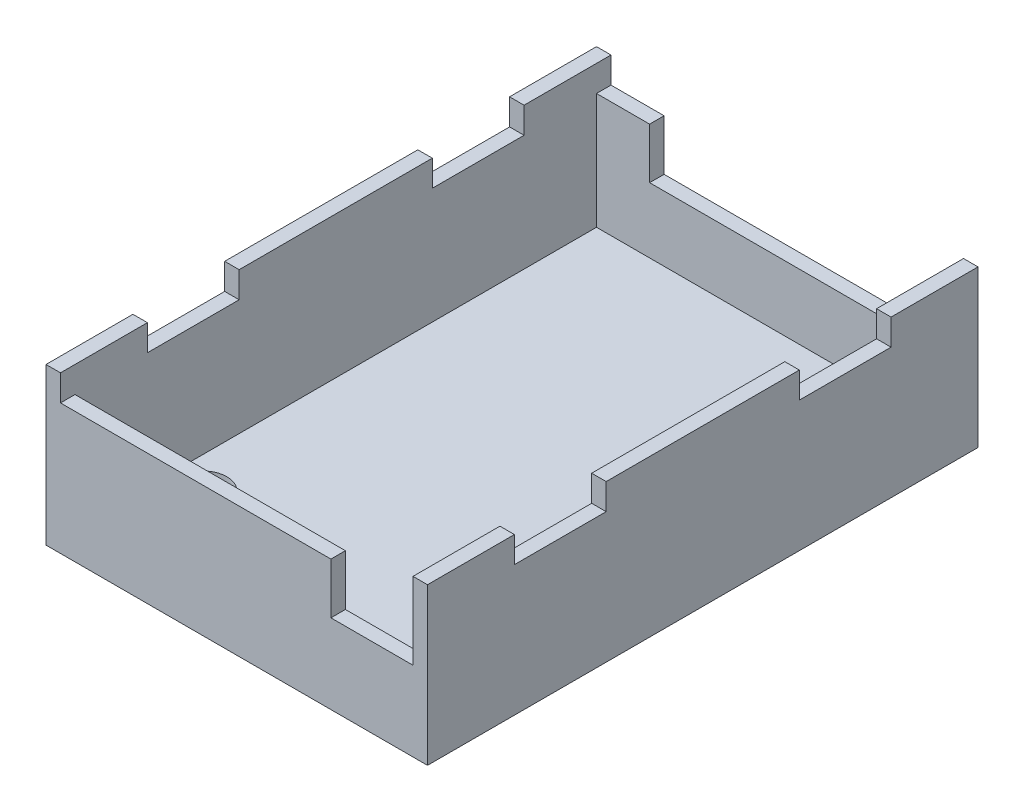
SolidWorks part; units mm, degrees
ref_plane "Front Plane" through (0, 0, 0) normal (0, 0, 1) x (1, 0, 0)
ref_plane "Top Plane" through (0, 0, 0) normal (0, 1, 0) x (1, 0, 0)
ref_plane "Right Plane" through (0, 0, 0) normal (1, 0, 0) x (0, 0, -1)
sketch "Sketch1" plane through (0, 0, 0) normal (0, 1, 0) x (1, 0, 0)
  line L1 (0, 0) -> (39.5, 0)
  line L2 (0, 0) -> (0, 57)
  line L3 (0, 57) -> (39.5, 57)
  line L4 (39.5, 0) -> (39.5, 57)
  dimension "D1" = 39.5
  dimension "D2" = 57
extrude "Boss-Extrude1" add sketch "Sketch1" along normal blind 1.5
sketch "Sketch3" plane through (0, 1.5, 0) normal (0, 1, 0) x (1, 0, 0)
  line L1 (0, 0) -> (39.5, 0)
  line L2 (0, 0) -> (0, 57)
  line L3 (0, 57) -> (39.5, 57)
  line L4 (39.5, 0) -> (39.5, 57)
  line L5 (1.5, 1.5) -> (38, 1.5)
  line L6 (1.5, 1.5) -> (1.5, 55.5)
  line L7 (1.5, 55.5) -> (38, 55.5)
  line L8 (38, 1.5) -> (38, 55.5)
  dimension "D1" = 54
  dimension "D2" = 36.5
  dimension "D3" = 1.5
  dimension "D4" = 1.5
extrude "Boss-Extrude2" add sketch "Sketch3" along normal blind 12
sketch "Sketch6" plane through (0, 0, 0) normal (0, 0, 1) x (1, 0, 0)
  line L0 (39.5, 13.5) -> (39.5, 0) construction
  line L1 (29.5, 14.23) -> (38, 14.23)
  line L2 (29.5, 14.23) -> (29.5, 8.23)
  line L3 (29.5, 8.23) -> (38, 8.23)
  line L4 (38, 14.23) -> (38, 8.23)
  line L5 (0, 0) -> (39.5, 0) construction
  point P4 (39.5, 6.75)
  dimension "D1" = 8.5
  dimension "D2" = 6
  dimension "D3" = 1.5
  dimension "D4" = 8.23
extrude "Cut-Extrude2" cut sketch "Sketch6" against normal blind 11.2
sketch "Sketch7" plane through (0, 0, -57) normal (0, 0, -1) x (-1, 0, 0)
  line L0 (-39.5, 13.5) -> (-39.5, 0) construction
  line L1 (-36.5, 14.23) -> (-7, 14.23)
  line L2 (-36.5, 14.23) -> (-36.5, 8.25)
  line L3 (-36.5, 8.25) -> (-7, 8.25)
  line L4 (-7, 14.23) -> (-7, 8.25)
  line L5 (-39.5, 0) -> (0, 0) construction
  dimension "D1" = 29.5
  dimension "D2" = 5.98
  dimension "D3" = 3
  dimension "D4" = 8.25
extrude "Cut-Extrude3" cut sketch "Sketch7" against normal blind 3.3
sketch "Sketch10" plane through (0, 13.5, 0) normal (0, 1, 0) x (1, 0, 0)
  line L0 (1.5, 55.5) -> (1.5, 1.5) construction
  line L1 (0, 57) -> (1.5, 57)
  line L2 (0, 57) -> (0, 48)
  line L3 (0, 48) -> (1.5, 48)
  line L4 (1.5, 57) -> (1.5, 48)
  line L5 (0, 57) -> (0, 0) construction
  line L6 (0, 38.5) -> (1.5, 38.5)
  line L7 (0, 38.5) -> (0, 18.5)
  line L8 (0, 18.5) -> (1.5, 18.5)
  line L9 (1.5, 38.5) -> (1.5, 18.5)
  line L10 (1.5, 55.5) -> (1.5, 1.5) construction
  line L11 (38, 1.5) -> (38, 55.5) construction
  line L12 (0, 0) -> (1.5, 0)
  line L13 (0, 0) -> (0, 9)
  line L14 (0, 9) -> (1.5, 9)
  line L15 (1.5, 0) -> (1.5, 9)
  line L16 (39.5, 57) -> (38, 57)
  line L17 (39.5, 57) -> (39.5, 48)
  line L18 (39.5, 48) -> (38, 48)
  line L19 (38, 57) -> (38, 48)
  line L20 (39.5, 0) -> (39.5, 57) construction
  line L21 (39.5, 38.5) -> (38, 38.5)
  line L22 (39.5, 38.5) -> (39.5, 18.5)
  line L23 (39.5, 18.5) -> (38, 18.5)
  line L24 (38, 38.5) -> (38, 18.5)
  line L25 (38, 0) -> (38, 55.5) construction
  line L27 (39.5, 0) -> (38, 0)
  line L28 (39.5, 0) -> (39.5, 9)
  line L29 (39.5, 9) -> (38, 9)
  line L30 (38, 0) -> (38, 9)
  dimension "D1" = 9
  dimension "D2" = 9
  dimension "D3" = 20
  dimension "D4" = 9.5
  dimension "D5" = 9.5
  dimension "D6" = 9
  dimension "D7" = 20
  dimension "D8" = 9
  dimension "D9" = 9.5
  dimension "D10" = 9.5
extrude "Boss-Extrude4" add sketch "Sketch10" along normal blind 2.7
sketch "Sketch11" plane through (0, 1.5, 0) normal (0, 1, 0) x (1, 0, 0)
  line L0 (7, 55.5) -> (36.5, 55.5) construction
  line L1 (30, 51.5) -> (37, 51.5)
  line L2 (30, 51.5) -> (30, 41.5)
  line L3 (30, 41.5) -> (37, 41.5)
  line L4 (37, 51.5) -> (37, 41.5)
  line L5 (38, 1.5) -> (38, 55.5) construction
  dimension "D1" = 10
  dimension "D2" = 7
  dimension "D3" = 4
  dimension "D4" = 1
extrude "Cut-Extrude4" cut sketch "Sketch11" against normal blind 7
sketch "Sketch12" plane through (0, 1.5, 0) normal (0, 1, 0) x (1, 0, 0)
  line L0 (1.5, 1.5) -> (29.5, 1.5) construction
  circle A0 centre (4.729, 11.5) radius 2.5
  dimension "D1" = 5
  dimension "D2" = 10
extrude "Cut-Extrude5" cut sketch "Sketch12" against normal blind 7
